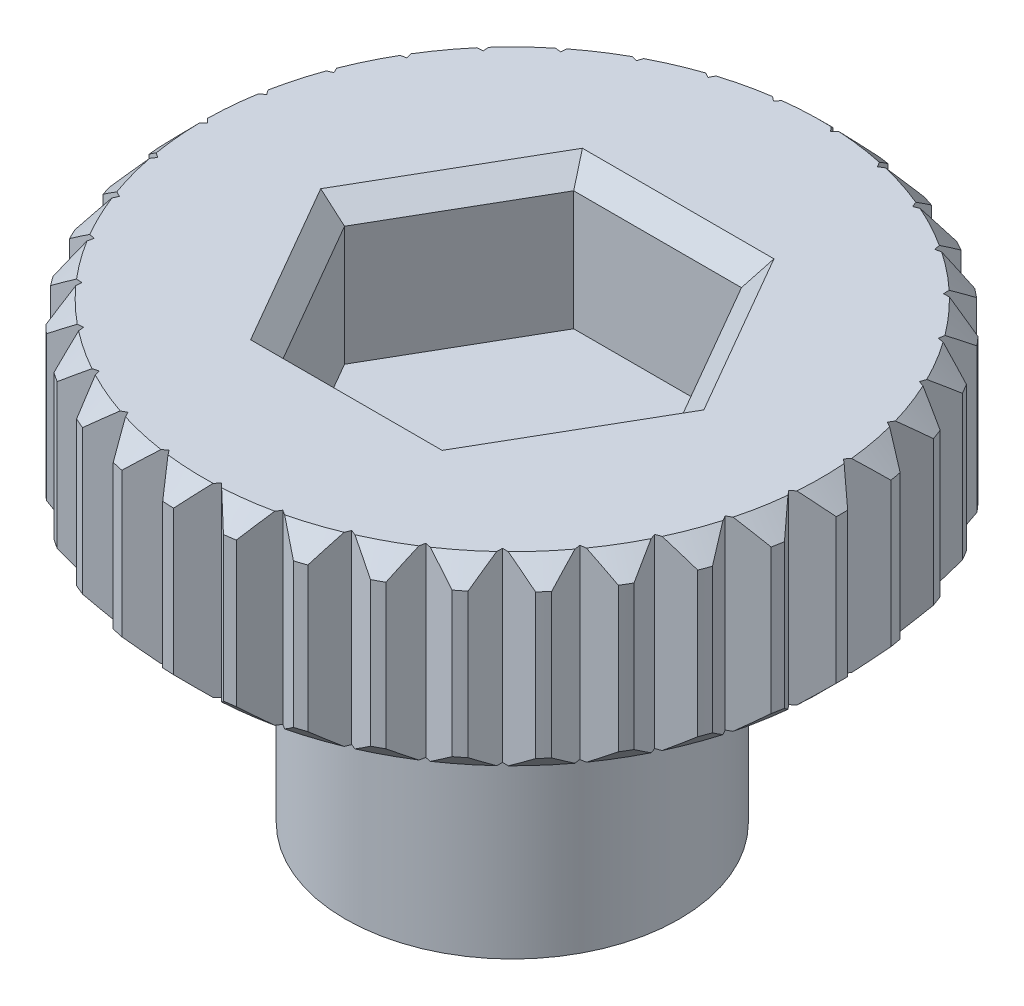
SolidWorks part; units mm, degrees
ref_plane "Front Plane" through (0, 0, 0) normal (0, 0, 1) x (1, 0, 0)
ref_plane "Top Plane" through (0, 0, 0) normal (0, 1, 0) x (1, 0, 0)
ref_plane "Right Plane" through (0, 0, 0) normal (1, 0, 0) x (0, 0, -1)
sketch "Layout sketch" plane through (0, 0, 0) normal (0, 0, 1) x (1, 0, 0)
  line L0 (0, 0) -> (0, 15.3642) construction
  line L1 (-4.05, 0) -> (-4.05, 6.5)
  line L2 (-4.05, 6.5) -> (-7.5, 6.5)
  line L3 (-8, 7) -> (-8, 10.5)
  line L4 (-7.5, 11) -> (-2.55, 11)
  line L5 (-2.05, 10.5) -> (-2.05, 0.5)
  line L6 (-2.55, 0) -> (-4.05, 0)
  line L7 (-8, 10.5) -> (-7.5, 11)
  line L8 (-2.55, 11) -> (-2.05, 10.5)
  line L9 (-2.05, 0.5) -> (-2.55, 0)
  line L10 (-7.5, 6.5) -> (-8, 7)
  point P6 (-8, 6.5)
  point P7 (-8, 11)
  point P8 (-2.05, 11)
  point P9 (-2.05, 0)
  dimension "D1" = 11
  dimension "D2" = 16
  dimension "D3" = 4.1
  dimension "D4" = 8.1
  dimension "D5" = 4.5
revolve "Body" add sketch "Layout sketch" angle 360 about L0
sketch "Sketch3" plane through (0, 11, 0) normal (0, 1, 0) x (1, 0, 0)
  line L0 (0, 0) -> (-12.543, 0) construction
  line L1 (-8.4, -1) -> (-8.4, 1)
  line L2 (-8.4, 1) -> (-7.4, 0)
  line L3 (-7.4, 0) -> (-8.4, -1)
  circle A0 centre (0, 0) radius 8 construction
  point P3 (-8, 0)
  point P6 (-8.4, 0)
  dimension "D1" = 1
  dimension "D2" = 0.6
extrude "Vertical knurl" cut sketch "Sketch3" against normal up to next
ref_axis "Central axis" through (0, 9.975, 0) along (0, -1, 0)
pattern_circular "Vertical knurl pattern" count 35 over 360 about axis through (0, 9.975, 0) along (0, -1, 0) of "Vertical knurl"
sketch "Sketch4" plane through (0, 11, 0) normal (0, 1, 0) x (1, 0, 0)
  line L1 (4.0703, 0) -> (2.0352, 3.525)
  line L2 (2.0352, 3.525) -> (-2.0352, 3.525)
  line L3 (-2.0352, 3.525) -> (-4.0703, 0)
  line L4 (-4.0703, 0) -> (-2.0352, -3.525)
  line L5 (-2.0352, -3.525) -> (2.0352, -3.525)
  line L6 (2.0352, -3.525) -> (4.0703, 0)
  circle A0 centre (0, 0) radius 3.525 construction
  dimension "D1" = 7.05
extrude "Cut-Extrude1" cut sketch "Sketch4" against normal blind 3.4
chamfer "Chamfer1" distance 0.5 angle 45 6 edges at (-3.0527, 11, 1.7625) (0, 11, 3.525) (3.0527, 11, 1.7625) (3.0527, 11, -1.7625) (0, 11, -3.525) (-3.0527, 11, -1.7625)
sketch "Sketch5" plane through (0, 7.6, 0) normal (0, 1, 0) x (1, 0, 0)
  circle A0 centre (0, 0) radius 2.05 construction
  circle A1 centre (0, 0) radius 2.05
extrude "Boss-Extrude1" add sketch "Sketch5" against normal blind 0.4
